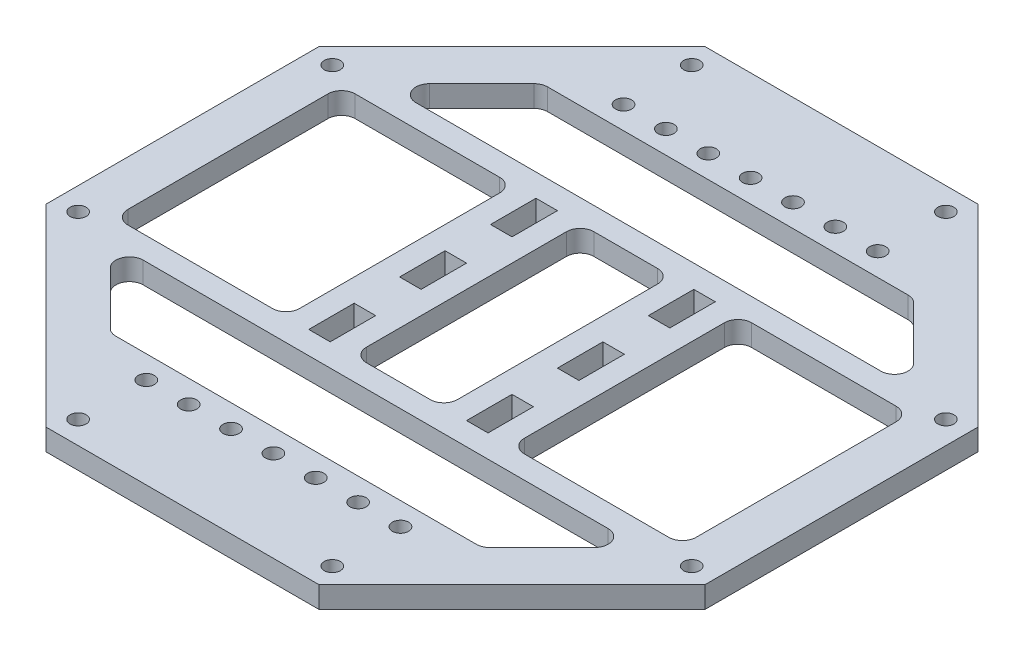
SolidWorks part; units mm, degrees
material "Custom Plastic"
ref_plane "Front Plane" through (0, 0, 0) normal (0, 0, 1) x (1, 0, 0)
ref_plane "Top Plane" through (0, 0, 0) normal (0, 1, 0) x (1, 0, 0)
ref_plane "Right Plane" through (0, 0, 0) normal (1, 0, 0) x (0, 0, -1)
ref_axis "Axis1" through (0, 6.2941, 0) along (0, -1, 0)
sketch "Sketch1" plane through (0, 0, 0) normal (0, 1, 0) x (1, 0, 0)
  line L1 (-38.1387, 92.075) -> (-92.075, 38.1387)
  line L2 (-92.075, 38.1387) -> (-92.075, -38.1387)
  line L3 (-92.075, -38.1387) -> (-38.1387, -92.075)
  line L4 (-38.1387, -92.075) -> (38.1387, -92.075)
  line L5 (38.1387, -92.075) -> (92.075, -38.1387)
  line L6 (92.075, -38.1387) -> (92.075, 38.1387)
  line L7 (92.075, 38.1387) -> (38.1387, 92.075)
  line L8 (38.1387, 92.075) -> (-38.1387, 92.075)
  circle A0 centre (0, 0) radius 92.075 construction
  dimension "D1" = 184.15
extrude "Base" add sketch "Sketch1" along normal blind 6
sketch "Sketch2" plane through (0, 6, 0) normal (0, 1, 0) x (1, 0, 0)
  line L0 (38.1387, 92.075) -> (-38.1387, 92.075) construction
  line L1 (35.5085, 85.725) -> (-35.5085, 85.725)
  line L2 (-35.5085, 85.725) -> (-85.725, 35.5085)
  line L3 (-85.725, 35.5085) -> (-85.725, -35.5085)
  line L4 (-85.725, -35.5085) -> (-35.5085, -85.725)
  line L5 (-35.5085, -85.725) -> (35.5085, -85.725)
  line L6 (35.5085, -85.725) -> (85.725, -35.5085)
  line L7 (85.725, -35.5085) -> (85.725, 35.5085)
  line L8 (85.725, 35.5085) -> (35.5085, 85.725)
  circle A0 centre (0, 0) radius 85.725 construction
  dimension "D1" = 6.35
hole_wizard "Mounting holes" positions "Sketch4" profile "Sketch3" hole size "#8" standard "ANSI Inch"
sketch "Sketch4" plane through (0, 6, 0) normal (0, 1, 0) x (1, 0, 0)
  point P0 (-35.5085, 85.725)
  point P8 (35.5085, 85.725)
  point P11 (85.725, 35.5085)
  point P14 (85.725, -35.5085)
  point P17 (35.5085, -85.725)
  point P20 (-35.5085, -85.725)
  point P23 (-85.725, -35.5085)
  point P26 (-85.725, 35.5085)
sketch "Sketch3" plane through (-35.5085, 6, -85.725) normal (1, 0, 0) x (0, 0, 1)
  line L0 (0, 0) -> (0, 5.9944)
  line L1 (0, 5.9944) -> (2.2479, 5.9944)
  line L2 (2.2479, 5.9944) -> (2.2479, 0)
  line L5 (2.2479, 0) -> (0, 0)
  line L10 (0, 5.9944) -> (-2.2479, 5.9944) construction
  line L11 (0, -6.35) -> (0, 107.95) construction
  dimension "Hole Dia." = 4.4958
  dimension "Hole Depth" = 5.9944
  dimension "Drill Angle" = 180
sketch "Sketch5" plane through (0, 6, 0) normal (0, 1, 0) x (1, 0, 0)
  line L0 (0, 92.075) -> (0, -92.075) construction
  line L1 (38.1387, 92.075) -> (-38.1387, 92.075) construction
  line L2 (-38.1387, -92.075) -> (38.1387, -92.075) construction
  line L3 (-19.05, 0) -> (0, 0) construction
  line L4 (-19.05, 6.35) -> (-19.05, 19.05) construction
  line L5 (-19.05, 19.05) -> (-25.05, 19.05)
  line L6 (-25.05, 19.05) -> (-25.05, 31.75)
  line L7 (-25.05, 31.75) -> (-19.05, 31.75)
  line L8 (-19.05, 31.75) -> (-19.05, 19.05)
  line L9 (-19.05, -6.35) -> (-19.05, -19.05) construction
  line L10 (-25.05, -19.05) -> (-19.05, -19.05)
  line L11 (-25.05, -19.05) -> (-25.05, -31.75)
  line L12 (-25.05, -31.75) -> (-19.05, -31.75)
  line L13 (-19.05, -19.05) -> (-19.05, -31.75)
  line L14 (-25.05, 6.35) -> (-25.05, -6.35)
  line L15 (-19.05, 6.35) -> (-19.05, -6.35)
  line L16 (-25.05, 6.35) -> (-19.05, 6.35)
  line L17 (-25.05, -6.35) -> (-19.05, -6.35)
  line L18 (19.05, -6.35) -> (19.05, -19.05) construction
  line L19 (19.05, 6.35) -> (19.05, 19.05) construction
  line L20 (25.05, 6.35) -> (19.05, 6.35)
  line L21 (19.05, 6.35) -> (19.05, -6.35)
  line L22 (25.05, 6.35) -> (25.05, -6.35)
  line L23 (19.05, -19.05) -> (19.05, -31.75)
  line L24 (25.05, -31.75) -> (19.05, -31.75)
  line L25 (25.05, -19.05) -> (25.05, -31.75)
  line L26 (19.05, 31.75) -> (19.05, 19.05)
  line L27 (25.05, 31.75) -> (19.05, 31.75)
  line L28 (25.05, 19.05) -> (25.05, 31.75)
  line L29 (19.05, 19.05) -> (25.05, 19.05)
  line L30 (25.05, -6.35) -> (19.05, -6.35)
  line L31 (25.05, -19.05) -> (19.05, -19.05)
  dimension "D1" = 12.7
  dimension "D2" = 6
  dimension "D3" = 19.05
extrude "4-bar mount" cut sketch "Sketch5" against normal through all
sketch "Sketch8" plane through (0, 6, 0) normal (0, 1, 0) x (1, 0, 0)
  line L0 (-63.5387, 66.675) -> (63.5387, 66.675) construction
  line L1 (-38.1387, 92.075) -> (-92.075, 38.1387) construction
  line L2 (92.075, 38.1387) -> (38.1387, 92.075) construction
  line L3 (38.1387, 92.075) -> (-38.1387, 92.075) construction
  line L4 (-35.5085, 85.725) -> (-35.5085, 66.675) construction
  line L5 (35.5085, 66.675) -> (35.5085, 85.725) construction
  circle A0 centre (-35.5085, 66.675) radius 2.2479
  circle A1 centre (-35.5085, 85.725) radius 2.2479 construction
  circle A2 centre (-23.6723, 66.675) radius 2.2479
  circle A3 centre (-11.8362, 66.675) radius 2.2479
  circle A4 centre (0, 66.675) radius 2.2479
  circle A5 centre (11.8362, 66.675) radius 2.2479
  circle A6 centre (23.6723, 66.675) radius 2.2479
  circle A7 centre (35.5085, 66.675) radius 2.2479
  circle A15 centre (35.5085, 85.725) radius 2.2479 construction
  dimension "D1" = 25.4
  dimension "D2" = 7
extrude "limit switch mount holes" cut sketch "Sketch8" against normal through all
pattern_circular "lim sw circ pattern" count 2 every 180 about axis through (0, 6.2941, 0) along (0, -1, 0) of "limit switch mount holes"
sketch "Sketch9" plane through (0, 6, 0) normal (0, 1, 0) x (1, 0, 0)
  line L0 (-19.05, 31.75) -> (-25.05, 31.75) construction
  line L1 (12.7, -31.75) -> (-12.7, -31.75)
  line L2 (12.7, -31.75) -> (12.7, 31.75)
  line L3 (12.7, 31.75) -> (-12.7, 31.75)
  line L4 (-12.7, -31.75) -> (-12.7, 31.75)
  line L5 (12.7, -31.75) -> (-12.7, 31.75) construction
  line L6 (12.7, 31.75) -> (-12.7, -31.75) construction
  line L7 (-19.05, -6.35) -> (-19.05, 6.35) construction
  line L8 (-25.05, -19.05) -> (-25.05, -31.75) construction
  line L9 (-79.375, 31.75) -> (-31.4, 31.75)
  line L10 (-79.375, 31.75) -> (-79.375, -31.75)
  line L11 (-79.375, -31.75) -> (-31.4, -31.75)
  line L12 (-31.4, 31.75) -> (-31.4, -31.75)
  line L13 (-92.075, 38.1387) -> (-92.075, -38.1387) construction
  line L14 (-25.05, -31.75) -> (-19.05, -31.75) construction
  line L15 (25.05, -6.35) -> (25.05, 6.35) construction
  line L16 (31.4, 31.75) -> (79.375, 31.75)
  line L17 (31.4, 31.75) -> (31.4, -31.75)
  line L18 (31.4, -31.75) -> (79.375, -31.75)
  line L19 (79.375, 31.75) -> (79.375, -31.75)
  line L20 (-74.1532, 38.1) -> (74.1532, 38.1)
  line L21 (74.1532, 38.1) -> (51.9282, 60.325)
  line L22 (51.9282, 60.325) -> (-51.9282, 60.325)
  line L23 (-51.9282, 60.325) -> (-74.1532, 38.1)
  line L24 (-38.1387, 92.075) -> (-92.075, 38.1387) construction
  line L25 (92.075, 38.1387) -> (38.1387, 92.075) construction
  line L26 (0, 31.75) -> (0, 38.1) construction
  line L27 (-92.075, 0) -> (92.075, 0) construction
  line L28 (92.075, -38.1387) -> (92.075, 38.1387) construction
  line L29 (-74.1532, -38.1) -> (74.1532, -38.1)
  line L30 (74.1532, -38.1) -> (51.9282, -60.325)
  line L31 (51.9282, -60.325) -> (-51.9282, -60.325)
  line L32 (-51.9282, -60.325) -> (-74.1532, -38.1)
  circle A0 centre (-23.6723, 66.675) radius 2.2479 construction
  point P0 (0, 0)
  point P14 (-25.05, -25.4)
  dimension "D5" = 6.35
  dimension "D1" = 6.35
  dimension "D2" = 6.35
  dimension "D3" = 12.7
  dimension "D4" = 6.35
  dimension "D6" = 6.35
  dimension "D7" = 12.7
extrude "Wire holes" cut sketch "Sketch9" against normal through all
fillet "Fillet1" radius 3.81 20 edges at (12.7, 3, 31.75) (-12.7, 3, 31.75) (-31.4, 3, 31.75) (74.1532, 3, -38.1) (79.375, 3, 31.75) (51.9282, 3, 60.325) (-51.9282, 3, 60.325) (31.4, 3, 31.75) (-79.375, 3, 31.75) (-74.1532, 3, -38.1) (-74.1532, 3, 38.1) (-79.375, 3, -31.75) (-12.7, 3, -31.75) (31.4, 3, -31.75) (-51.9282, 3, -60.325) (74.1532, 3, 38.1) (79.375, 3, -31.75) (51.9282, 3, -60.325) (12.7, 3, -31.75) (-31.4, 3, -31.75)
equation "\"MAT_THICKNESS\"=0.23622"
equation "\"D1@Base\"=\"MAT_THICKNESS\""
